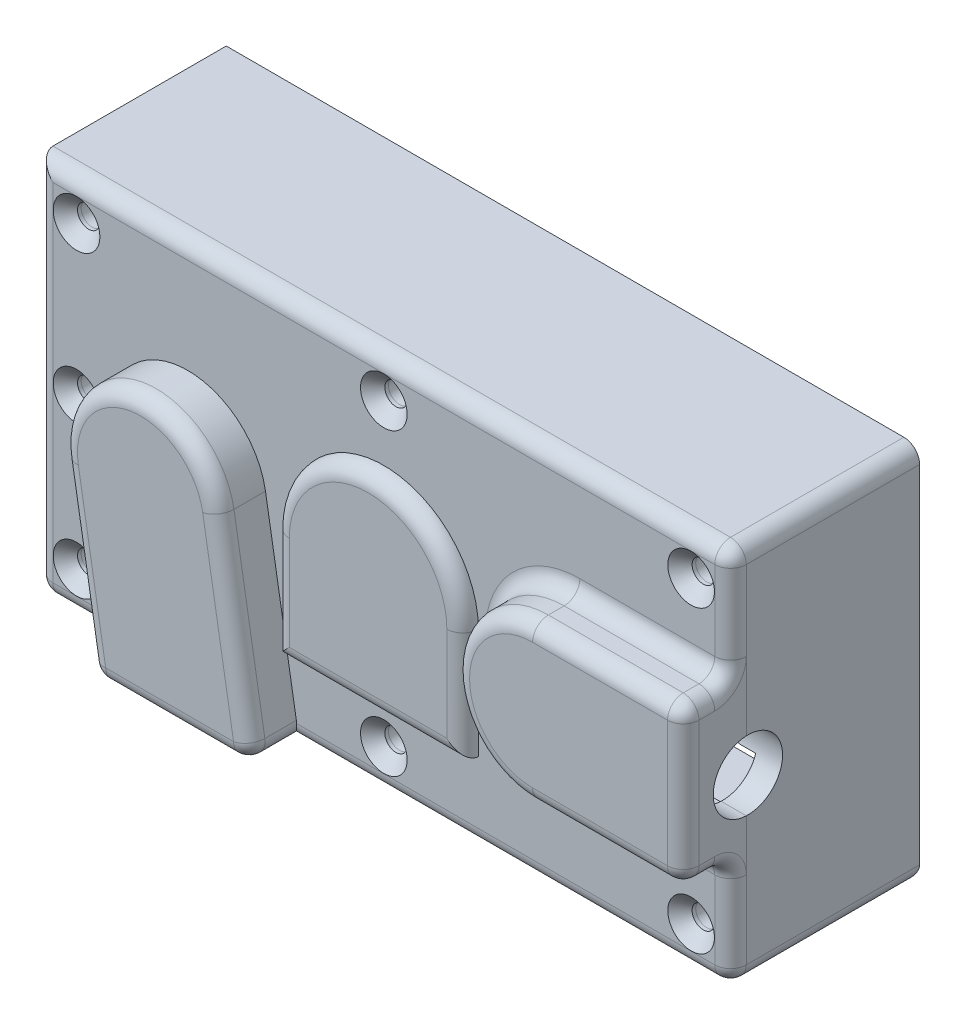
SolidWorks part; units mm, degrees
note: The reader was unsure of these and kept them because the rebuilt part matched: shared geometry of "Sketch13<3>".
material "ABS"
ref_plane "X-Y Datum" through (0, 0, 0) normal (0, 0, 1) x (1, 0, 0)
ref_plane "X-Z Datum" through (0, 0, 0) normal (0, 1, 0) x (1, 0, 0)
ref_plane "Y-Z Datum" through (0, 0, 0) normal (1, 0, 0) x (0, 0, -1)
sketch "Sketch3" plane through (0, 0, 0) normal (0, 0, 1) x (1, 0, 0)
  line L1 (-69.85, 38.1) -> (69.85, 38.1)
  line L2 (-69.85, 38.1) -> (-69.85, -38.1)
  line L3 (-69.85, -38.1) -> (69.85, -38.1)
  line L4 (69.85, 38.1) -> (69.85, -38.1)
  line L5 (-69.85, 38.1) -> (69.85, -38.1) construction
  line L6 (-69.85, -38.1) -> (69.85, 38.1) construction
  point P0 (0, 0)
  dimension "D1" = 139.7
  dimension "D2" = 76.2
extrude "Boss-Extrude1" add sketch "Sketch3" along normal blind 38.1
ref_plane "Plane1" through (0, 0, 0) normal (0, -1, 0) x (-1, 0, 0)
sketch "Sketch13" plane through (0, 0, 38.1) normal (0, 0, 1) x (1, 0, 0)
  line L0 (-69.85, -0.1574) -> (69.85, -0.1574) construction
  line L1 (-69.85, 38.1) -> (-69.85, -38.1) construction
  line L2 (69.85, -38.1) -> (69.85, 38.1) construction
  line L3 (0, 38.1) -> (0, -38.1) construction
  line L4 (69.85, 38.1) -> (-69.85, 38.1) construction
  line L5 (-69.85, -38.1) -> (69.85, -38.1) construction
  line L7 (-55.3747, -0.1574) -> (-23.6247, -0.1574) construction
  line L8 (-55.3747, -0.1574) -> (-55.3747, -38.1) construction
  line L9 (-55.3747, -38.1) -> (-23.6247, -38.1) construction
  line L10 (-23.6247, -0.1574) -> (-23.6247, -38.1) construction
  line L13 (-19.05, -0.1574) -> (19.05, -0.1574) construction
  line L14 (-19.05, -0.1574) -> (-19.05, -22.3824)
  line L15 (19.05, -0.1574) -> (19.05, -22.3824)
  line L16 (-19.05, -22.3824) -> (19.05, -22.3824)
  line L17 (39.4997, -16.0324) -> (69.85, -16.0324)
  line L18 (39.4997, 15.7176) -> (69.85, 15.7176)
  line L19 (69.85, -16.0324) -> (69.85, 15.7176)
  line L20 (-55.1536, -2.7975) -> (-49.1996, -38.1)
  line L21 (-23.8458, 2.4828) -> (-17.0012, -38.1)
  line L22 (-49.1996, -38.1) -> (-17.0012, -38.1)
  circle A0 centre (-39.4997, -0.1574) radius 15.875 construction
  arc A1 (-55.3747, -0.1574) -> (-23.6247, -0.1574) centre (-39.4997, -0.1574) cw construction
  circle A3 centre (0, -0.1574) radius 19.05 construction
  arc A4 (-19.05, -0.1574) -> (19.05, -0.1574) centre (0, -0.1574) cw
  circle A5 centre (39.4997, -0.1574) radius 15.875 construction
  arc A6 (39.4997, -16.0324) -> (39.4997, 15.7176) centre (39.4997, -0.1574) cw
  arc A7 (-55.1536, -2.7975) -> (-23.8458, 2.4828) centre (-39.4997, -0.1574) cw
  circle A26 centre (-39.4997, -0.1574) radius 4.25 construction
  point P41 (-17.0012, -38.1)
  dimension "D1" = 31.75
  dimension "D3" = 38.1
  dimension "D2" = 17.0012
  dimension "D4" = 22.225
extrude "Boss-Extrude3" add sketch "Sketch13" along normal blind 9.525 contours A1 L10 L9 L8 | A6 L18 L19 L17 | A7 L21 L22 L20
extrude "Boss-Extrude4" add sketch "Sketch13<3>" along normal blind 3.175 contours A4 L14 L16 L15
sketch "Sketch13<3>" plane through (0, 0, 38.1) normal (0, 0, 1) x (1, 0, 0) same geometry as "Sketch13"
shell "Shell1" thickness 5.08
sketch "Sketch9" plane through (0, 0, 0) normal (0, 0, 1) x (1, 0, 0)
  line L0 (69.85, -38.1) -> (69.85, 38.1) construction
  line L1 (-69.85, 38.1) -> (-69.85, -38.1) construction
  line L2 (0, 38.1) -> (0, -38.1) construction
  line L3 (69.85, 38.1) -> (-69.85, 38.1) construction
  line L4 (-69.85, 0) -> (69.85, 0) construction
  line L6 (-4.0411, 30.1625) -> (4.0411, 30.1625) construction
  line L7 (-4.0411, 38.1) -> (4.0411, 38.1)
  line L8 (-61.9125, 4.0411) -> (-61.9125, -4.0411) construction
  line L9 (-61.9125, 4.0411) -> (-69.85, 4.0411)
  line L10 (-61.9125, -4.0411) -> (-69.85, -4.0411)
  line L11 (-69.85, 4.0411) -> (-69.85, -4.0411)
  line L12 (-69.85, 38.1) -> (-69.85, -38.1) construction
  line L13 (-4.0411, -30.1625) -> (4.0411, -30.1625) construction
  line L14 (-4.0411, -30.1625) -> (-4.0411, -38.1)
  line L15 (4.0411, -30.1625) -> (4.0411, -38.1)
  line L16 (-4.0411, -38.1) -> (4.0411, -38.1)
  line L17 (-69.85, -38.1) -> (-49.1996, -38.1) construction
  line L18 (4.0411, 30.1625) -> (4.0411, 38.1)
  line L19 (-4.0411, 30.1625) -> (-4.0411, 38.1)
  line L20 (61.9125, 4.0411) -> (61.9125, -4.0411) construction
  line L21 (69.85, 4.0411) -> (69.85, -4.0411)
  line L22 (61.9125, -4.0411) -> (69.85, -4.0411)
  line L23 (61.9125, 4.0411) -> (69.85, 4.0411)
  line L24 (-69.85, -38.1) -> (69.85, -38.1) construction
  circle A0 centre (-61.9125, -30.1625) radius 7.9375 construction
  circle A1 centre (-61.9125, 30.1625) radius 7.9375 construction
  circle A2 centre (61.9125, -30.1625) radius 7.9375 construction
  circle A3 centre (61.9125, 30.1625) radius 7.9375 construction
  circle A4 centre (-61.9125, 0) radius 7.9375 construction
  circle A5 centre (0, 30.1625) radius 7.9375 construction
  circle A6 centre (61.9125, 0) radius 7.9375 construction
  circle A7 centre (0, -30.1625) radius 7.9375 construction
  circle A9 centre (-61.9125, -30.1625) radius 4.0411
  circle A10 centre (-61.9125, 0) radius 4.0411 construction
  circle A13 centre (-61.9125, 30.1625) radius 4.0411
  circle A14 centre (61.9125, -30.1625) radius 4.0411
  circle A16 centre (61.9125, 30.1625) radius 4.0411
  circle A17 centre (0, -30.1625) radius 4.0411 construction
  arc A18 (-61.9125, 4.0411) -> (-61.9125, -4.0411) centre (-61.9125, 0) cw
  arc A19 (-4.0411, -30.1625) -> (4.0411, -30.1625) centre (0, -30.1625) cw
  circle A20 centre (0, 30.1625) radius 4.0411 construction
  arc A21 (-4.0411, 30.1625) -> (4.0411, 30.1625) centre (0, 30.1625) ccw
  circle A22 centre (61.9125, 0) radius 4.0411 construction
  arc A23 (61.9125, 4.0411) -> (61.9125, -4.0411) centre (61.9125, 0) ccw
  point P2 (0, 0)
  point P3 (0, 0)
  dimension "D1" = 15.875
extrude "Boss-Extrude2" add sketch "Sketch9" along normal up to surface (38.1 mm away)
sketch "Sketch6" plane through (0, 0, 0) normal (0, -1, 0) x (1, 0, 0)
  line L0 (-69.85, 0) -> (-64.77, 0) construction
  line L1 (-69.85, 0) -> (69.85, 0) construction
  line L2 (-68.6435, 1.3208) -> (-65.9765, 1.3208)
  line L3 (-67.31, 1.3208) -> (-67.31, 0) construction
  line L4 (-68.6435, 1.3208) -> (-68.7012, 0)
  line L7 (-65.9765, 1.3208) -> (-65.9188, 0)
  arc A0 (-68.7012, 0) -> (-65.9188, 0) centre (-67.31, 0.1064) ccw
  dimension "D1" = 5.08
  dimension "D2" = 1.3208
  dimension "D3" = 2.667
  dimension "D4" = 92.5
sketch "Sketch7" plane through (0, 0, 0) normal (0, 0, -1) x (-1, 0, 0)
  line L0 (-69.85, 38.1) -> (69.85, 38.1) construction
  line L1 (-64.77, 35.56) -> (64.77, 35.56)
  line L2 (-67.31, 33.02) -> (-67.31, -33.02)
  line L3 (-64.77, -35.56) -> (64.77, -35.56)
  line L4 (67.31, 33.02) -> (67.31, -33.02)
  line L6 (-69.85, -38.1) -> (-69.85, 38.1) construction
  line L7 (69.85, 38.1) -> (69.85, -38.1) construction
  line L9 (69.85, -38.1) -> (-69.85, -38.1) construction
  arc A0 (64.77, 35.56) -> (67.31, 33.02) centre (64.77, 33.02) cw
  arc A1 (64.77, -35.56) -> (67.31, -33.02) centre (64.77, -33.02) ccw
  arc A2 (-67.31, -33.02) -> (-64.77, -35.56) centre (-64.77, -33.02) ccw
  arc A3 (-64.77, 35.56) -> (-67.31, 33.02) centre (-64.77, 33.02) ccw
  point P21 (67.31, -33.02)
  dimension "D6" = 2.54
  dimension "D1" = 2.54
  dimension "D2" = 2.54
  dimension "D3" = 2.54
  dimension "D4" = 2.54
sweep "O Ring Cut" cut profiles "Sketch6" path "Sketch7"
fillet "Fillet2" radius 3.175 29 edges at (-69.85, 0, 38.1) (0, 38.1, 38.1) (19.05, -11.2699, 41.275) (0, -22.3824, 41.275) (-19.05, -11.2699, 41.275) (0, 18.8926, 41.275) (-69.85, -38.1, 19.05) (69.85, 38.1, 19.05) (69.85, -38.1, 19.05) (69.85, -27.0662, 38.1) (69.85, 26.9088, 38.1) (69.85, -16.0324, 42.8625) (69.85, -0.1574, 47.625) (69.85, 15.7176, 42.8625) (54.6748, -16.0324, 38.1) (54.6748, 15.7176, 38.1) (54.6748, 15.7176, 47.625) (54.6748, -16.0324, 47.625) (23.6247, -0.1574, 47.625) (23.6247, -0.1574, 38.1) (26.4244, -38.1, 38.1) (-59.5248, -38.1, 38.1) (0, -38.1, 0) (-49.1996, -38.1, 42.8625) (-17.0012, -38.1, 42.8625) (-42.1398, 15.4965, 47.625) (-20.4235, -17.8086, 47.625) (-33.1004, -38.1, 47.625) (-52.1766, -20.4488, 47.625)
hole_wizard "M4 Clearance Hole1" positions "Sketch10" profile "Sketch11" hole size "M4" standard "ANSI Metric"
sketch "Sketch10" plane through (0, 0, 0) normal (0, 0, -1) x (-1, 0, 0)
  point P0 (-61.9125, 0)
  point P3 (-61.9125, 30.1625)
  point P6 (0, 30.1625)
  point P9 (61.9125, 30.1625)
  point P12 (61.9125, 0)
  point P15 (61.9125, -30.1625)
  point P18 (0, -30.1625)
  point P21 (-61.9125, -30.1625)
sketch "Sketch11" plane through (61.9125, 0, 0) normal (1, 0, 0) x (0, 1, 0)
  line L0 (0, 0) -> (0, 13.3519)
  line L1 (0, 13.3519) -> (2.25, 12)
  line L2 (2.25, 12) -> (2.25, 0.025)
  line L3 (2.25, 0.025) -> (2.275, 0)
  line L5 (2.275, 0) -> (0, 0)
  line L6 (-2.25, 0.025) -> (-2.275, 0) construction
  line L10 (0, 13.3519) -> (-2.25, 12) construction
  line L11 (0, -6.35) -> (0, 107.95) construction
  dimension "Hole Dia." = 4.5
  dimension "Hole Depth" = 12
  dimension "Near C'Sink Dia." = 4.55
  dimension "Near C'Sink Angle" = 90
  dimension "Drill Angle" = 118
hole_wizard "CSK for M4 Flat Head Machine Screw1" positions "Sketch16" profile "Sketch17" countersink size "M4" standard "ANSI Metric"
sketch "Sketch16" plane through (0, 0, 38.1) normal (0, 0, 1) x (1, 0, 0)
  point P0 (-61.9125, 30.1625)
  point P3 (0, 30.1625)
  point P6 (61.9125, 30.1625)
  point P12 (61.9125, -30.1625)
  point P15 (0, -30.1625)
  point P18 (-61.9125, -30.1625)
  point P21 (-61.9125, 0)
  point P25 (0, 0)
sketch "Sketch17" plane through (-61.9125, 30.1625, 38.1) normal (1, 0, 0) x (0, -1, 0)
  line L0 (0, 0) -> (0, 13.2899)
  line L1 (0, 13.2899) -> (2.25, 11.938)
  line L2 (2.25, 11.938) -> (2.25, 2.45)
  line L3 (2.25, 2.45) -> (4.7, 0)
  line L5 (4.7, 0) -> (0, 0)
  line L6 (-2.25, 2.45) -> (-4.7, 0) construction
  line L10 (0, 13.2899) -> (-2.25, 11.938) construction
  line L11 (0, -6.35) -> (0, 107.95) construction
  dimension "Hole Dia." = 4.5
  dimension "Hole Depth" = 11.938
  dimension "Near C'Sink Dia." = 9.4
  dimension "Near C'Sink Angle" = 90
  dimension "Drill Angle" = 118
sketch "Sketch15" plane through (0, -38.1, 0) normal (0, -1, 0) x (1, 0, 0)
  line L0 (-20.7565, 34.925) -> (-20.7565, 44.45) construction
  line L6 (-32.1865, 44.45) -> (-32.1865, 34.6) construction
  circle A0 centre (-32.1865, 34.6) radius 6.985
  point P2 (-33.949, 34.6)
  dimension "D1" = 13.97
  dimension "D2" = 9.85
  dimension "D3" = 11.43
extrude "Cut-Extrude1" cut sketch "Sketch15" against normal up to surface (5.08 mm away)
sketch "Sketch23" plane through (69.85, 0, 0) normal (1, 0, 0) x (0, 0, -1)
  line L0 (-44.45, -1.9354) -> (-34.6, -1.9354) construction
  line L2 (-44.45, -12.8574) -> (-41.275, -12.8574) construction
  circle A0 centre (-34.6, -1.9354) radius 6.985
  dimension "D2" = 13.97
  dimension "D1" = 9.85
  dimension "D3" = 10.922
extrude "Cut-Extrude2" cut sketch "Sketch23" against normal blind 13.716
ref_plane "Cut Plane" through (0, 0, 34.925) normal (0, 0, -1) x (-1, 0, 0)
sketch "Sketch19" plane through (0, -38.1, 0) normal (0, -1, 0) x (1, 0, 0)
  line L0 (-66.675, 9.525) -> (66.675, 9.525) construction
  line L3 (-66.675, 34.925) -> (-66.675, 3.175) construction
  line L4 (66.675, 3.175) -> (66.675, 34.925) construction
  line L5 (-66.675, 0) -> (66.675, 0) construction
  text T0 "HVD" font "Century Gothic" height 19.05
  dimension "D1" = 9.525
extrude "HVD text" cut sketch "Sketch19" against normal blind 1.5875
sketch "Sketch22" plane through (-69.85, 0, 0) normal (-1, 0, 0) x (0, 0, 1)
  line L0 (9.525, -38.1) -> (9.525, 34.925) construction
  text T0 "<b>HVD</b>" font "Century Gothic" height 19.05
  point P6 (0, 0)
extrude "HVD text top" cut sketch "Sketch22" against normal blind 1.5875
split "Split2" trim tools "Cut Plane" bodies to split 118 resulting bodies 116 117
equation "\"shell width\"= 0.2"
equation "\"D1@Shell1\"=\"shell width\""
equation "\"D1@Sketch6\"=\"shell width\""
equation "\"D1@Sketch7\"=\"shell width\"/2"
equation "\"D2@Sketch7\"=\"shell width\"/2"
equation "\"D3@Sketch7\"=\"shell width\"/2"
equation "\"D4@Sketch7\"=\"shell width\"/2"
equation "\"D6@Sketch7\"=\"shell width\"/2"
